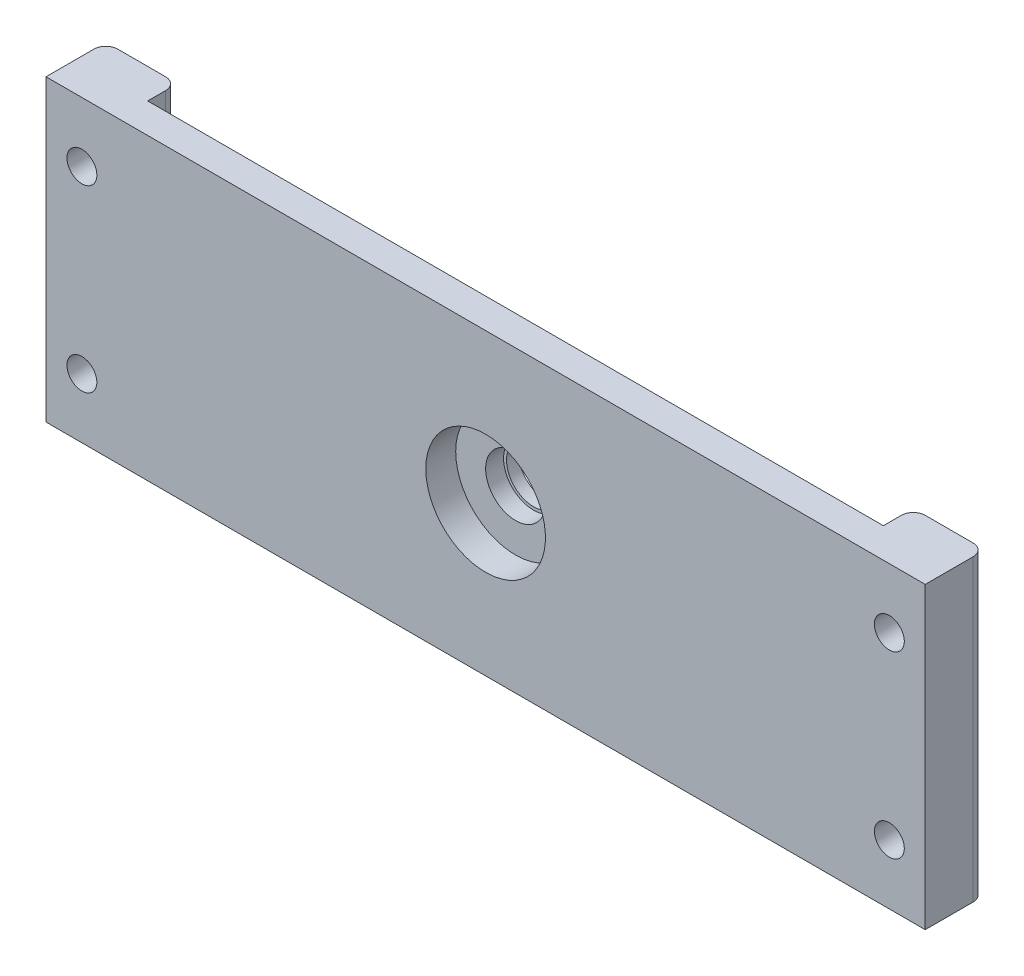
SolidWorks part; units mm, degrees
ref_plane "Alzado" through (0, 0, 0) normal (0, 0, 1) x (1, 0, 0)
ref_plane "Planta" through (0, 0, 0) normal (0, 1, 0) x (1, 0, 0)
ref_plane "Vista lateral" through (0, 0, 0) normal (1, 0, 0) x (0, 0, -1)
sketch "Croquis1" plane through (0, 0, 0) normal (0, 0, 1) x (1, 0, 0)
  line L1 (-73.5, -25) -> (73.5, -25)
  line L2 (-73.5, -25) -> (-73.5, 25)
  line L3 (-73.5, 25) -> (73.5, 25)
  line L4 (73.5, -25) -> (73.5, 25)
  line L5 (-73.5, -25) -> (73.5, 25) construction
  line L6 (-73.5, 25) -> (73.5, -25) construction
  point P0 (0, 0)
  dimension "D1" = 147
  dimension "D2" = 50
extrude "Saliente-Extruir1" add sketch "Croquis1" along normal blind 5
sketch "Croquis2" plane through (0, 0, 0) normal (0, 0, -1) x (-1, 0, 0)
  circle A0 centre (0, 0) radius 10
  dimension "D1" = 20
extrude "Cortar-Extruir1" cut sketch "Croquis2" against normal through all both and the other way through all
sketch "Croquis3" plane through (0, 0, 0) normal (0, 0, -1) x (-1, 0, 0)
  circle A0 centre (0, 0) radius 5
  circle A1 centre (0, 0) radius 11
  dimension "D1" = 10
  dimension "D2" = 22
extrude "Saliente-Extruir2" add sketch "Croquis3" along normal blind 5
fillet "Redondeo1" radius 3 1 edges at (-11, 0, -5)
sketch "Croquis4" plane through (0, 0, -5) normal (0, 0, -1) x (-1, 0, 0)
  circle A0 centre (0, 0) radius 4.5
  circle A1 centre (0, 0) radius 5 construction
  circle A2 centre (0, 0) radius 5
  dimension "D1" = 0.5
extrude "Saliente-Extruir3" add sketch "Croquis4" against normal blind 2 separate body
sketch "Croquis5" plane through (0, 0, 0) normal (0, 0, -1) x (-1, 0, 0)
  line L0 (73.5, -25) -> (-73.5, -25) construction
  line L1 (-73.5, 25) -> (-61.5, 25)
  line L2 (-73.5, 25) -> (-73.5, -25)
  line L3 (-73.5, -25) -> (-61.5, -25)
  line L4 (-61.5, 25) -> (-61.5, -25)
  line L5 (0, 0) -> (0, 65.4326) construction
  line L6 (73.5, -25) -> (61.5, -25)
  line L7 (61.5, 25) -> (61.5, -25)
  line L8 (73.5, 25) -> (61.5, 25)
  line L9 (73.5, 25) -> (73.5, -25)
  dimension "D1" = 12
extrude "Saliente-Extruir4" add sketch "Croquis5" along normal blind 5
sketch "Croquis6" plane through (0, 0, -5) normal (0, 0, -1) x (-1, 0, 0)
  line L0 (-67.5, 25) -> (-67.5, -24.6707) construction
  line L1 (-61.5, 25) -> (-73.5, 25) construction
  line L2 (67.5, 25) -> (67.5, -25) construction
  line L3 (73.5, 25) -> (61.5, 25) construction
  line L4 (61.5, -25) -> (73.5, -25) construction
  line L5 (0, 0) -> (0, 60.8717) construction
  circle A0 centre (67.5, 15) radius 4.25
  circle A1 centre (67.5, -15) radius 4.25
  circle A2 centre (-67.5, -15) radius 4.25
  circle A3 centre (-67.5, 15) radius 4.25
  dimension "D1" = 8.5
  dimension "D2" = 8.5
  dimension "D3" = 10
  dimension "D4" = 10
extrude "Cortar-Extruir2" cut sketch "Croquis6" against normal blind 6 and the other way through all
sketch "Croquis7" plane through (0, 0, 1) normal (0, 0, -1) x (-1, 0, 0)
  circle A0 centre (67.5, -15) radius 4.25 construction
  circle A1 centre (67.5, 15) radius 4.25 construction
  circle A2 centre (-67.5, -15) radius 4.25 construction
  circle A3 centre (-67.5, 15) radius 4.25 construction
  circle A4 centre (67.5, -15) radius 4.25 construction
  circle A5 centre (67.5, 15) radius 4.25 construction
  circle A6 centre (-67.5, -15) radius 4.25 construction
  circle A7 centre (-67.5, 15) radius 4.25 construction
  circle A8 centre (-67.5, 15) radius 2.5
  circle A10 centre (67.5, 15) radius 2.5
  circle A11 centre (67.5, -15) radius 2.5
  circle A12 centre (-67.5, -15) radius 2.5
  dimension "D1" = 1.75
extrude "Cortar-Extruir3" cut sketch "Croquis7" against normal through all
fillet "Redondeo2" radius 2 4 edges at (73.5, 0, -5) (61.5, 0, -5) (-73.5, 0, -5) (-61.5, 0, -5)
